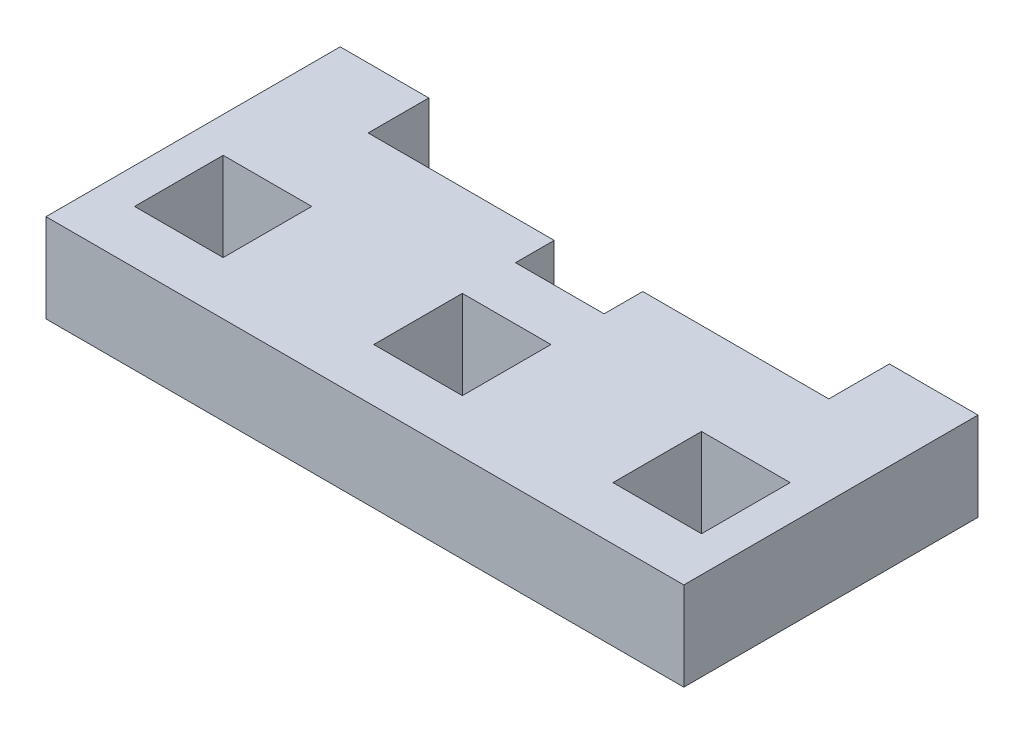
SolidWorks part; units mm, degrees
ref_plane "Front Plane" through (0, 0, 0) normal (0, 0, 1) x (1, 0, 0)
ref_plane "Top Plane" through (0, 0, 0) normal (0, 1, 0) x (1, 0, 0)
ref_plane "Right Plane" through (0, 0, 0) normal (1, 0, 0) x (0, 0, -1)
sketch "Sketch1" plane through (0, 0, 0) normal (0, 1, 0) x (1, 0, 0)
  line L0 (-22.86, 0) -> (22.86, 0) construction
  line L1 (-22.86, -6.985) -> (22.86, -6.985)
  line L2 (-22.86, -6.985) -> (-22.86, 9.7575)
  line L3 (-16.51, 9.7575) -> (-3.175, 9.7575)
  line L4 (22.86, -6.985) -> (22.86, 9.7575)
  line L5 (0, 6.985) -> (0, -6.985) construction
  line L6 (-3.175, 9.7575) -> (-3.175, 6.985)
  line L7 (-3.175, 6.985) -> (3.175, 6.985)
  line L8 (3.175, 6.985) -> (3.175, 9.7575)
  line L9 (3.175, 9.7575) -> (16.51, 9.7575)
  line L10 (-20.32, 3.175) -> (-13.97, -3.175) construction
  line L11 (-3.175, 3.175) -> (3.175, 3.175)
  line L12 (-3.175, 3.175) -> (-3.175, -3.175)
  line L13 (-3.175, -3.175) -> (3.175, -3.175)
  line L15 (22.86, 9.7575) -> (22.86, 14.1025)
  line L16 (3.175, 3.175) -> (3.175, -3.175)
  line L17 (-3.175, 3.175) -> (3.175, -3.175) construction
  line L18 (-3.175, -3.175) -> (3.175, 3.175) construction
  line L19 (-13.97, 3.175) -> (-20.32, -3.175) construction
  line L20 (13.97, 3.175) -> (20.32, -3.175) construction
  line L21 (13.97, -3.175) -> (20.32, 3.175) construction
  line L22 (20.32, -3.175) -> (13.97, -3.175)
  line L23 (20.32, -3.175) -> (20.32, 3.175)
  line L24 (20.32, 3.175) -> (13.97, 3.175)
  line L25 (13.97, -3.175) -> (13.97, 3.175)
  line L26 (22.86, 14.1025) -> (16.51, 14.1025)
  line L27 (16.51, 14.1025) -> (16.51, 9.7575)
  line L28 (-16.51, 14.1025) -> (-16.51, 9.7575)
  line L29 (-22.86, 14.1025) -> (-16.51, 14.1025)
  line L30 (-13.97, -3.175) -> (-13.97, 3.175)
  line L31 (-20.32, 3.175) -> (-13.97, 3.175)
  line L32 (-20.32, -3.175) -> (-20.32, 3.175)
  line L33 (-20.32, -3.175) -> (-13.97, -3.175)
  line L34 (-22.86, 9.7575) -> (-22.86, 14.1025)
  point P8 (0, 0)
  point P12 (0, 6.985)
  point P16 (0, 0)
  point P22 (-17.145, 0)
  point P23 (17.145, 0)
  dimension "D1" = 45.72
  dimension "D2" = 3.81
  dimension "D3" = 6.35
  dimension "D4" = 3.81
  dimension "D5" = 13.97
  dimension "D6" = 6.35
  dimension "D7" = 2.54
  dimension "D8" = 10.795
  dimension "D9" = 2.7725
  dimension "D10" = 4.345
  dimension "D11" = 6.35
  dimension "D12" = 21.0875
extrude "Boss-Extrude1" add sketch "Sketch1" along normal blind 6.35
equation "\"Ball Diameter\"= 1.75in"
equation "\"Sheet Thickness\"= 0.25in"
equation "\"Screw Diameter\"= .17in"
equation "\"Robot Diameter\"= 14in"
equation "\"Castor Screw Diameter\"= 0.22in"
equation "\"Wheel Diameter\" = 4in"
equation "\"Nut Diameter\" = 8.4mm"
equation "\"Nut Height\" = 2.9mm"
equation "\"Screw Height\" = 0.55in"
equation "\"Pulley Diameter\" = 1in"
equation "\"Reactor Height\" = 14in"
equation "\"Elevator Height\" = 11.5in"
equation "\"Elevator Width\" = \"Ball Diameter\" + 0.25in"
equation "\"Elevator Bearing Diameter\" = sqr(2*(\"Sheet Thickness\"^2)) + 0.2in"
equation "\"Elevator Axle Endcap Diameter\" = \"Pulley Diameter\" + 0.25in"
equation "\"Elevator Axle Length\" = \"Elevator Width\" + 8*\"Sheet Thickness\""
equation "\"Elevator Clearance from Axis\" = 3.5in"
equation "\"D1@Sketch1\"=\"Elevator Width\"-0.2in"
equation "\"D3@Sketch1\" = \"Sheet Thickness\""
equation "\"D6@Sketch1\"=\"Sheet Thickness\""
equation "\"D9@Sketch1\"=(0.3in - ((\"Elevator Axle Endcap Diameter\"-\"Pulley Diameter\")/2 - 1.1mm))/2"
equation "\"D10@Sketch1\"=(\"Elevator Axle Endcap Diameter\"-\"Pulley Diameter\")/2 - 1.1mm + 2.27mm"
equation "\"D1@Boss-Extrude1\"=\"Sheet Thickness\""
equation "\"Ball Radius\" = \"Ball Diameter\"/2"
equation "\"Claw Horizontal Seperation\" = (\"Elevator Width\"/2) - (1.5 * \"Sheet Thickness\") - 0.15in"
